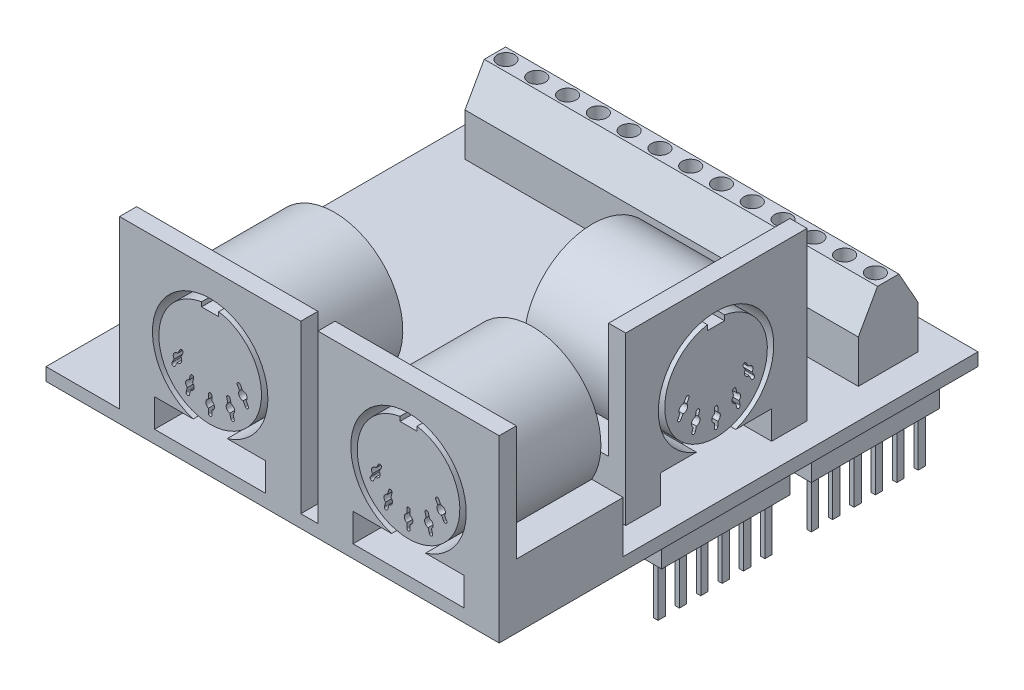
SolidWorks part; units mm, degrees
ref_plane "Front Plane" through (0, 0, 0) normal (0, 0, 1) x (1, 0, 0)
ref_plane "Top Plane" through (0, 0, 0) normal (0, 1, 0) x (1, 0, 0)
ref_plane "Right Plane" through (0, 0, 0) normal (1, 0, 0) x (0, 0, -1)
sketch "Sketch1" plane through (0, 0, 0) normal (0, 1, 0) x (1, 0, 0)
  line L1 (-26.5, -28) -> (26.5, -28)
  line L2 (-26.5, -28) -> (-26.5, 28)
  line L3 (-26.5, 28) -> (26.5, 28)
  line L4 (26.5, -28) -> (26.5, 28)
  line L5 (-26.5, -28) -> (26.5, 28) construction
  line L6 (-26.5, 28) -> (26.5, -28) construction
  point P0 (0, 0)
  dimension "D1" = 53
  dimension "D2" = 56
extrude "Boss-Extrude1" add sketch "Sketch1" along normal blind 1.5
sketch "Sketch2" plane through (0, 1.5, 0) normal (0, 1, 0) x (1, 0, 0)
  line L0 (-26.5, 28) -> (-26.5, -28) construction
  line L1 (-23, 24.5) -> (23, 24.5)
  line L2 (-23, 24.5) -> (-23, 17.5)
  line L3 (-23, 17.5) -> (23, 17.5)
  line L4 (23, 24.5) -> (23, 17.5)
  line L5 (26.5, -28) -> (26.5, 28) construction
  line L6 (26.5, 28) -> (-26.5, 28) construction
  dimension "D1" = 3.5
  dimension "D2" = 3.5
  dimension "D3" = 3.5
  dimension "D4" = 7
extrude "Boss-Extrude2" add sketch "Sketch2" along normal blind 5
sketch "Sketch4" plane through (-23, 0, 0) normal (-1, 0, 0) x (0, 0, 1)
  line L0 (-24.5, 6.5) -> (-17.5, 6.5)
  line L1 (-17.5, 6.5) -> (-19.75, 10.5)
  line L2 (-19.75, 10.5) -> (-22.25, 10.5)
  line L3 (-22.25, 10.5) -> (-24.5, 6.5)
  line L4 (-21, 10.5) -> (-21, 6.5) construction
  dimension "D1" = 4
  dimension "D2" = 2.5
extrude "Boss-Extrude3" add sketch "Sketch4" against normal up to surface (46 mm away) up to face at (23, 4, -21)
sketch "Sketch5" plane through (0, 10.5, 0) normal (0, 1, 0) x (1, 0, 0)
  line L0 (-23, 21) -> (23, 21) construction
  line L1 (-23, 24.5) -> (-23, 17.5) construction
  line L2 (23, 22.25) -> (23, 19.75) construction
  circle A0 centre (-21.7, 21) radius 1
  circle A1 centre (-18.1, 21) radius 1
  circle A2 centre (-14.5, 21) radius 1
  circle A3 centre (-10.9, 21) radius 1
  circle A4 centre (-7.3, 21) radius 1
  circle A5 centre (-3.7, 21) radius 1
  circle A6 centre (-0.1, 21) radius 1
  circle A7 centre (3.5, 21) radius 1
  circle A8 centre (7.1, 21) radius 1
  circle A9 centre (10.7, 21) radius 1
  circle A10 centre (14.3, 21) radius 1
  circle A11 centre (17.9, 21) radius 1
  circle A12 centre (21.5, 21) radius 1
  dimension "D1" = 2
  dimension "D2" = 1.3
  dimension "D3" = 13
extrude "Cut-Extrude1" cut sketch "Sketch5" against normal blind 2
sketch "Sketch6" plane through (0, 0, 28) normal (0, 0, 1) x (1, 0, 0)
  line L0 (-26.5, 1.5) -> (26.5, 1.5) construction
  line L1 (-17.9, 1.5) -> (3.3, 1.5)
  line L2 (-17.9, 1.5) -> (-17.9, 21)
  line L3 (-17.9, 21) -> (3.3, 21)
  line L4 (3.3, 1.5) -> (3.3, 21)
  line L5 (-23, 1.5) -> (23, 1.5) construction
  line L6 (5.3, 1.5) -> (26.5, 1.5)
  line L7 (5.3, 1.5) -> (5.3, 21)
  line L8 (5.3, 21) -> (26.5, 21)
  line L9 (26.5, 1.5) -> (26.5, 21)
  dimension "D1" = 21.2
  dimension "D2" = 19.5
  dimension "D3" = 21.2
  dimension "D4" = 19.5
  dimension "D5" = 2
extrude "Boss-Extrude4" add sketch "Sketch6" against normal blind 2 separate body
sketch "Sketch7" plane through (0, 0, 26) normal (0, 0, -1) x (-1, 0, 0)
  line L0 (-15.9, 21) -> (-15.9, 1.5) construction
  line L1 (-26.5, 21) -> (-5.3, 21) construction
  line L2 (-23, 1.5) -> (23, 1.5) construction
  line L3 (-15.9, 11.5) -> (7.2714, 11.5) construction
  line L4 (7.3, 21) -> (7.3, 7.5) construction
  line L5 (-3.3, 21) -> (17.9, 21) construction
  line L7 (-5.3, 21) -> (-5.3, 1.5) construction
  line L8 (-26.5, 1.5) -> (-5.3, 1.5)
  line L9 (-26.5, 1.5) -> (-26.5, 7.5)
  line L10 (-26.5, 7.5) -> (-22.8282, 7.5)
  line L12 (-5.3, 1.5) -> (-5.3, 7.5)
  line L13 (-8.9718, 7.5) -> (-5.3, 7.5)
  line L14 (-26.5, 1.5) -> (26.5, 1.5) construction
  line L15 (17.9, 7.5) -> (14.1996, 7.5)
  line L16 (17.9, 7.5) -> (17.9, 1.5)
  line L17 (17.9, 1.5) -> (-3.3, 1.5)
  line L18 (-3.3, 7.5) -> (-3.3, 1.5)
  line L19 (-3.3, 1.5) -> (-3.3, 21) construction
  line L20 (17.9, 21) -> (17.9, 1.5) construction
  line L21 (0.3432, 7.5) -> (-3.3, 7.5)
  line L22 (7.3, 3.5001) -> (7.3, 1.5) construction
  arc A0 (-8.9718, 7.5) -> (-22.8282, 7.5) centre (-15.9, 11.5) ccw
  arc A1 (14.1996, 7.5) -> (0.3432, 7.5) centre (7.2714, 11.5) ccw
  point P6 (-15.9, 11.5)
  dimension "D2" = 16
  dimension "D3" = 16
  dimension "D1" = 10
  dimension "D4" = 6
extrude "Boss-Extrude5" add sketch "Sketch7" along normal blind 12.5
sketch "Sketch8" plane through (0, 0, 28) normal (0, 0, 1) x (1, 0, 0)
  line L0 (-17.9, 21) -> (3.3, 1.5) construction
  line L1 (3.3, 21) -> (-17.9, 1.5) construction
  line L2 (-7.3, 17.25) -> (-7.3, 16.65) construction
  line L3 (-8.3, 16.65) -> (-6.3, 16.65)
  line L4 (-6.3, 16.65) -> (-6.3, 17.1661)
  line L5 (-8.3, 16.65) -> (-8.3, 17.1661)
  line L6 (-11.1219, 10.0698) -> (-3.4781, 10.0698) construction
  line L7 (-9.6748, 8.0313) -> (-4.9252, 8.0313) construction
  line L8 (-11.1219, 10.0698) -> (-9.6748, 8.0313) construction
  line L9 (-9.6748, 8.0313) -> (-7.3, 7.25) construction
  line L10 (-7.3, 7.25) -> (-4.9252, 8.0313) construction
  line L11 (-4.9252, 8.0313) -> (-3.4781, 10.0698) construction
  line L12 (-7.3, 6.25) -> (-7.3, 8.25) construction
  line L13 (-7.5, 6.25) -> (-7.5, 6.7917)
  line L14 (-7.1, 6.25) -> (-7.1, 6.7917)
  line L15 (-4.6757, 7.0629) -> (-5.1747, 8.9996) construction
  line L16 (-4.8694, 7.013) -> (-5.0046, 7.5376)
  line L17 (-4.4821, 7.1128) -> (-4.6172, 7.6374)
  line L18 (-3.0082, 9.1871) -> (-3.9479, 10.9526) construction
  line L19 (-3.1847, 9.0931) -> (-3.4393, 9.5713)
  line L20 (-2.8316, 9.2811) -> (-3.0862, 9.7593)
  line L21 (-9.9243, 7.0629) -> (-9.4253, 8.9996) construction
  line L22 (-10.1179, 7.1128) -> (-9.9828, 7.6374)
  line L23 (-9.7306, 7.013) -> (-9.5954, 7.5376)
  line L24 (-11.5918, 9.1871) -> (-10.6521, 10.9526) construction
  line L25 (-11.7684, 9.2811) -> (-11.5138, 9.7593)
  line L26 (-11.4153, 9.0931) -> (-11.1607, 9.5713)
  line L27 (-7.3, 17.25) -> (-10.6521, 10.9526) construction
  line L28 (-7.3, 17.25) -> (-3.9479, 10.9526) construction
  line L29 (-7.3, 17.25) -> (-9.4253, 8.9996) construction
  line L30 (-7.3, 17.25) -> (-5.1747, 8.9996) construction
  line L31 (-11.0832, 10.5683) -> (-10.8286, 11.0465)
  line L32 (-10.7301, 10.3804) -> (-10.4755, 10.8586)
  line L33 (4.3, 1.5) -> (4.3, 27.7192) construction
  line L34 (-9.7542, 8.5249) -> (-9.619, 9.0495)
  line L35 (-9.3668, 8.4251) -> (-9.2317, 8.9497)
  line L36 (3.3, 1.5) -> (5.3, 1.5) construction
  line L37 (15.9, 1.5) -> (15.9, 11.25) construction
  line L38 (-7.5, 7.7083) -> (-7.5, 8.25)
  line L39 (-7.1, 7.7083) -> (-7.1, 8.25)
  line L40 (15.9, 17.25) -> (13.7747, 8.9996) construction
  line L41 (15.9, 17.25) -> (18.0253, 8.9996) construction
  line L42 (-5.2332, 8.4251) -> (-5.3683, 8.9497)
  line L43 (-4.8458, 8.5249) -> (-4.981, 9.0495)
  line L44 (15.9, 17.25) -> (12.5479, 10.9526) construction
  line L45 (15.9, 17.25) -> (19.2521, 10.9526) construction
  line L46 (-3.8699, 10.3804) -> (-4.1245, 10.8586)
  line L47 (-3.5168, 10.5683) -> (-3.7714, 11.0465)
  line L48 (20.1918, 9.1871) -> (19.2521, 10.9526) construction
  line L49 (18.5243, 7.0629) -> (18.0253, 8.9996) construction
  line L50 (11.6082, 9.1871) -> (12.5479, 10.9526) construction
  line L51 (13.2757, 7.0629) -> (13.7747, 8.9996) construction
  line L52 (15.9, 6.25) -> (15.9, 8.25) construction
  line L53 (13.5252, 8.0313) -> (12.0781, 10.0698) construction
  line L54 (15.9, 7.25) -> (13.5252, 8.0313) construction
  line L55 (18.2748, 8.0313) -> (15.9, 7.25) construction
  line L56 (19.7219, 10.0698) -> (18.2748, 8.0313) construction
  line L57 (18.2748, 8.0313) -> (13.5252, 8.0313) construction
  line L58 (19.7219, 10.0698) -> (12.0781, 10.0698) construction
  line L59 (15.9, 17.25) -> (15.9, 16.65) construction
  line L60 (17.89, 4.8) -> (22.4, 4.8)
  line L61 (22.4, 4.8) -> (22.4, 1.5)
  line L62 (9.4, 4.8) -> (13.91, 4.8)
  line L63 (9.4, 1.5) -> (9.4, 4.8)
  line L64 (22.4, 1.5) -> (9.4, 1.5)
  line L65 (12.1168, 10.5683) -> (12.3714, 11.0465)
  line L66 (12.4699, 10.3804) -> (12.7245, 10.8586)
  line L67 (13.4458, 8.5249) -> (13.581, 9.0495)
  line L68 (13.8332, 8.4251) -> (13.9683, 8.9497)
  line L69 (15.7, 7.7083) -> (15.7, 8.25)
  line L70 (16.1, 7.7083) -> (16.1, 8.25)
  line L71 (17.9668, 8.4251) -> (17.8317, 8.9497)
  line L72 (18.3542, 8.5249) -> (18.219, 9.0495)
  line L73 (19.3301, 10.3804) -> (19.0755, 10.8586)
  line L74 (19.6832, 10.5683) -> (19.4286, 11.0465)
  line L75 (20.0153, 9.0931) -> (19.7607, 9.5713)
  line L76 (20.3684, 9.2811) -> (20.1138, 9.7593)
  line L77 (18.3306, 7.013) -> (18.1954, 7.5376)
  line L78 (18.7179, 7.1128) -> (18.5828, 7.6374)
  line L79 (11.4316, 9.2811) -> (11.6862, 9.7593)
  line L80 (11.7847, 9.0931) -> (12.0393, 9.5713)
  line L81 (13.0821, 7.1128) -> (13.2172, 7.6374)
  line L82 (-17.9, 1.5) -> (3.3, 1.5) construction
  line L83 (-13.8, 1.5) -> (-0.8, 1.5)
  line L84 (-0.8, 1.5) -> (-0.8, 4.8)
  line L85 (-0.8, 4.8) -> (-5.31, 4.8)
  line L86 (-13.8, 4.8) -> (-13.8, 1.5)
  line L87 (-7.3, 1.5) -> (-7.3, 11.25) construction
  line L88 (-9.29, 4.8) -> (-13.8, 4.8)
  line L89 (13.4694, 7.013) -> (13.6046, 7.5376)
  line L90 (15.7, 6.25) -> (15.7, 6.7917)
  line L91 (16.1, 6.25) -> (16.1, 6.7917)
  line L92 (16.9, 16.65) -> (16.9, 17.1661)
  line L93 (14.9, 16.65) -> (14.9, 17.1661)
  line L94 (16.9, 16.65) -> (14.9, 16.65)
  arc A0 (-5.31, 4.8) -> (-9.29, 4.8) centre (-7.3, 11.25) ccw
  arc A1 (-8.3, 17.1661) -> (-6.3, 17.1661) centre (-7.3, 11.25) ccw
  arc A2 (-7.5, 7.7083) -> (-7.5, 6.7917) centre (-7.3, 7.25) ccw
  arc A3 (-9.5954, 7.5376) -> (-9.3668, 8.4251) centre (-9.6748, 8.0313) ccw
  arc A4 (-4.8005, 7.5471) -> (-4.8458, 8.5249) centre (-4.9252, 8.0313) ccw
  arc A5 (-3.0862, 9.7593) -> (-3.5168, 10.5683) centre (-3.4781, 10.0698) ccw
  arc A6 (-11.0832, 10.5683) -> (-11.5138, 9.7593) centre (-11.1219, 10.0698) ccw
  circle A7 centre (-7.3, 11.25) radius 4 construction
  arc A8 (-7.5, 6.25) -> (-7.1, 6.25) centre (-7.3, 6.25) ccw
  arc A9 (-7.1, 8.25) -> (-7.5, 8.25) centre (-7.3, 8.25) ccw
  arc A10 (-4.8694, 7.013) -> (-4.4821, 7.1128) centre (-4.6757, 7.0629) ccw
  arc A11 (-4.981, 9.0495) -> (-5.3683, 8.9497) centre (-5.1747, 8.9996) ccw
  arc A12 (-3.1847, 9.0931) -> (-2.8316, 9.2811) centre (-3.0082, 9.1871) ccw
  arc A13 (-3.7714, 11.0465) -> (-4.1245, 10.8586) centre (-3.9479, 10.9526) ccw
  arc A14 (-10.1179, 7.1128) -> (-9.7306, 7.013) centre (-9.9243, 7.0629) ccw
  arc A15 (-9.2317, 8.9497) -> (-9.619, 9.0495) centre (-9.4253, 8.9996) ccw
  arc A16 (-11.7684, 9.2811) -> (-11.4153, 9.0931) centre (-11.5918, 9.1871) ccw
  arc A17 (-10.4755, 10.8586) -> (-10.8286, 11.0465) centre (-10.6521, 10.9526) ccw
  arc A18 (-11.1607, 9.5713) -> (-10.7301, 10.3804) centre (-11.1219, 10.0698) ccw
  arc A19 (-9.7542, 8.5249) -> (-9.9828, 7.6374) centre (-9.6748, 8.0313) ccw
  arc A20 (-7.1, 6.7917) -> (-7.1, 7.7083) centre (-7.3, 7.25) ccw
  arc A21 (-5.2332, 8.4251) -> (-5.0046, 7.5376) centre (-4.9252, 8.0313) ccw
  arc A22 (-3.8699, 10.3804) -> (-3.4393, 9.5713) centre (-3.4781, 10.0698) ccw
  circle A23 centre (15.9, 11.25) radius 4 construction
  arc A24 (12.4699, 10.3804) -> (12.0393, 9.5713) centre (12.0781, 10.0698) cw
  arc A25 (13.8332, 8.4251) -> (13.6046, 7.5376) centre (13.5252, 8.0313) cw
  arc A26 (15.7, 6.7917) -> (15.7, 7.7083) centre (15.9, 7.25) cw
  arc A27 (18.3542, 8.5249) -> (18.5828, 7.6374) centre (18.2748, 8.0313) cw
  arc A28 (19.7607, 9.5713) -> (19.3301, 10.3804) centre (19.7219, 10.0698) cw
  arc A29 (19.0755, 10.8586) -> (19.4286, 11.0465) centre (19.2521, 10.9526) cw
  arc A30 (20.3684, 9.2811) -> (20.0153, 9.0931) centre (20.1918, 9.1871) cw
  arc A31 (17.8317, 8.9497) -> (18.219, 9.0495) centre (18.0253, 8.9996) cw
  arc A32 (18.7179, 7.1128) -> (18.3306, 7.013) centre (18.5243, 7.0629) cw
  arc A33 (12.3714, 11.0465) -> (12.7245, 10.8586) centre (12.5479, 10.9526) cw
  arc A34 (11.7847, 9.0931) -> (11.4316, 9.2811) centre (11.6082, 9.1871) cw
  arc A35 (13.581, 9.0495) -> (13.9683, 8.9497) centre (13.7747, 8.9996) cw
  arc A36 (13.4694, 7.013) -> (13.0821, 7.1128) centre (13.2757, 7.0629) cw
  arc A37 (15.7, 8.25) -> (16.1, 8.25) centre (15.9, 8.25) cw
  arc A38 (16.1, 6.25) -> (15.7, 6.25) centre (15.9, 6.25) cw
  arc A39 (19.6832, 10.5683) -> (20.1138, 9.7593) centre (19.7219, 10.0698) cw
  arc A40 (11.6862, 9.7593) -> (12.1168, 10.5683) centre (12.0781, 10.0698) cw
  arc A41 (13.4005, 7.5471) -> (13.4458, 8.5249) centre (13.5252, 8.0313) cw
  arc A42 (18.1954, 7.5376) -> (17.9668, 8.4251) centre (18.2748, 8.0313) cw
  arc A43 (16.1, 7.7083) -> (16.1, 6.7917) centre (15.9, 7.25) cw
  arc A44 (16.9, 17.1661) -> (14.9, 17.1661) centre (15.9, 11.25) cw
  arc A45 (13.91, 4.8) -> (17.89, 4.8) centre (15.9, 11.25) cw
  point P8 (-7.3, 11.25)
  point P30 (-7.3, 7.25)
  point P37 (-4.9252, 8.0313)
  point P44 (-3.4781, 10.0698)
  point P50 (-9.6748, 8.0313)
  point P58 (-11.1219, 10.0698)
  dimension "D1" = 13.5
  dimension "D2" = 12
  dimension "D4" = 1
  dimension "D5" = 8
  dimension "D8" = 0.2
  dimension "D3" = 2
  dimension "D6" = 2.5
  dimension "D7" = 2
  dimension "D9" = 3.3
  dimension "D10" = 13
  dimension "D11" = 0.6
extrude "Cut-Extrude2" cut sketch "Sketch8" against normal blind 5 contours A0 A1 L5 L3 L4 | L26 A18 L32 A17 L31 A6 L25 A16 | L34 A19 L22 A14 L23 A3 L35 A15 | L14 A20 L39 A9 L38 A2 L13 A8 | L42 A21 L16 A10 L17 A4 L43 A11 | L46 A22 L19 A12 L20 A5 L47 A13 | A44 L61 | A40 L79 A34 L80 A24 L66 A33 L65 | A36 L89 A25 L68 A35 L67 | A43 L70 A37 L69 A26 L90 A38 L91 | A42 L77 A32 L78 A27 L72 A31 L71 | A39 L74 A29 L73 A28 L75 A30 L76 region at (-7.3, 7.25, 28) region at (-4.9252, 8.0313, 28) region at (-3.4781, 10.0698, 28) region at (-9.6748, 8.0312, 28) region at (-11.1219, 10.0698, 28) region at (20.145, 4.5868, 28) region at (12.0781, 10.0698, 28) region at (13.5252, 8.0313, 28) region at (15.9, 7.25, 28) region at (18.2748, 8.0312, 28) region at (19.7219, 10.0698, 28) region at (-13.5868, 3.15, 28)
sketch "Sketch9" plane through (26.5, 0, 0) normal (1, 0, 0) x (0, 0, -1)
  line L0 (-13.5, 1.5) -> (28, 1.5) construction
  line L1 (-10.2, 1.5) -> (11, 1.5)
  line L2 (-10.2, 1.5) -> (-10.2, 21)
  line L3 (-10.2, 21) -> (11, 21)
  line L4 (11, 1.5) -> (11, 21)
  line L5 (-26, 21) -> (-28, 21) construction
  line L7 (-28, 21) -> (-28, 0) construction
  dimension "D1" = 21.2
  dimension "D2" = 39
extrude "Boss-Extrude6" add sketch "Sketch9" against normal blind 2 from offset 3 separate body offset against normal yes
sketch "Sketch11" plane through (21.5, 0, 0) normal (-1, 0, 0) x (0, 0, 1)
  line L0 (-0.4, 21) -> (-0.4, 1.5) construction
  line L1 (-11, 21) -> (10.2, 21) construction
  line L2 (10.2, 1.5) -> (-11, 1.5) construction
  line L3 (10.2, 21) -> (10.2, 1.5) construction
  line L4 (-11, 1.5) -> (10.2, 1.5)
  line L5 (-11, 1.5) -> (-11, 7.5)
  line L6 (-11, 7.5) -> (-7.3282, 7.5)
  line L7 (10.2, 1.5) -> (10.2, 7.5)
  line L8 (6.5282, 7.5) -> (10.2, 7.5)
  arc A0 (6.5282, 7.5) -> (-7.3282, 7.5) centre (-0.4, 11.5) ccw
  dimension "D2" = 16
  dimension "D1" = 10
  dimension "D3" = 6
extrude "Boss-Extrude7" add sketch "Sketch11" along normal blind 12.5
sketch "Sketch13" plane through (23.5, 0, 0) normal (1, 0, 0) x (0, 0, -1)
  line L0 (-10.2, 21) -> (11, 1.5) construction
  line L1 (-10.2, 1.5) -> (11, 1.5) construction
  line L2 (0.3632, 16.1486) -> (0.3632, 1.5) construction
  line L3 (-6.1, 1.5) -> (6.8265, 1.5)
  line L7 (0.3632, 17.0631) -> (0.3632, 16.4631) construction
  line L8 (-0.6368, 16.4631) -> (1.3632, 16.4631)
  line L9 (1.3632, 16.4631) -> (1.3632, 17.0631)
  line L10 (-0.6368, 16.4631) -> (-0.6368, 17.0631)
  line L11 (-3.4587, 9.9668) -> (4.1852, 9.9668) construction
  line L12 (-2.0116, 7.9283) -> (2.738, 7.9283) construction
  line L13 (-3.4587, 9.9668) -> (-2.0116, 7.9283) construction
  line L14 (-2.0116, 7.9283) -> (0.3632, 7.147) construction
  line L15 (0.3632, 7.147) -> (2.738, 7.9283) construction
  line L16 (2.738, 7.9283) -> (4.1852, 9.9668) construction
  line L17 (0.3632, 6.147) -> (0.3632, 8.147) construction
  line L18 (0.1633, 6.1525) -> (0.1633, 6.6887)
  line L19 (0.5631, 6.1534) -> (0.5631, 6.6887)
  line L20 (2.9896, 6.9604) -> (2.4864, 8.8961) construction
  line L21 (2.7897, 6.9582) -> (2.6661, 7.4335)
  line L22 (3.186, 6.9982) -> (3.0465, 7.5348)
  line L23 (4.6594, 9.0864) -> (3.711, 10.8473) construction
  line L24 (4.4753, 9.0081) -> (4.2273, 9.4686)
  line L25 (4.8354, 9.1812) -> (4.5786, 9.6582)
  line L26 (-2.2632, 6.9604) -> (-1.7599, 8.8961) construction
  line L27 (-2.4567, 7.0108) -> (-2.3204, 7.535)
  line L28 (-2.0696, 6.9101) -> (-1.9333, 7.4344)
  line L29 (-3.9329, 9.0864) -> (-2.9845, 10.8473) construction
  line L30 (-4.1058, 9.1869) -> (-3.852, 9.6581)
  line L31 (-3.7568, 8.9916) -> (-3.4999, 9.4685)
  line L32 (0.3632, 17.0631) -> (-2.9845, 10.8473) construction
  line L33 (0.3632, 17.0631) -> (3.711, 10.8473) construction
  line L34 (0.3632, 17.0631) -> (-1.7599, 8.8961) construction
  line L35 (0.3632, 17.0631) -> (2.4864, 8.8961) construction
  line L36 (-3.4174, 10.4651) -> (-3.1636, 10.9363)
  line L37 (-3.0653, 10.2755) -> (-2.8084, 10.7524)
  line L38 (-2.0897, 8.4221) -> (-1.9519, 8.9523)
  line L39 (-1.7027, 8.3215) -> (-1.5664, 8.8458)
  line L40 (0.1633, 7.6053) -> (0.1633, 8.153)
  line L41 (0.5631, 7.6053) -> (0.5631, 8.1534)
  line L42 (2.4366, 8.3272) -> (2.2866, 8.9043)
  line L43 (2.8159, 8.4222) -> (2.6828, 8.9339)
  line L44 (3.7918, 10.2755) -> (3.5349, 10.7524)
  line L45 (4.144, 10.4651) -> (3.8871, 10.9421)
  line L46 (-6.1368, 1.5) -> (6.8632, 1.5)
  line L47 (6.8632, 1.5) -> (6.8632, 4.8)
  line L48 (6.8632, 4.8) -> (2.6606, 4.8)
  line L49 (-6.1368, 4.8) -> (-6.1368, 1.5)
  line L50 (0.3632, 1.5) -> (0.3632, 11.147) construction
  line L51 (-1.9342, 4.8) -> (-6.1368, 4.8)
  arc A2 (2.6606, 4.8) -> (-1.9342, 4.8) centre (0.3632, 11.147) ccw
  arc A3 (-0.6368, 17.0631) -> (1.3632, 17.0631) centre (0.3632, 11.147) ccw
  arc A4 (0.1633, 7.6053) -> (0.1633, 6.6887) centre (0.3632, 7.147) ccw
  arc A5 (-1.9333, 7.4344) -> (-1.7027, 8.3215) centre (-2.0116, 7.9283) ccw
  arc A6 (3.0465, 7.5348) -> (2.8159, 8.4222) centre (2.738, 7.9283) ccw
  arc A7 (4.5786, 9.6582) -> (4.144, 10.4651) centre (4.1852, 9.9668) ccw
  arc A8 (-3.4174, 10.4651) -> (-3.852, 9.6581) centre (-3.4587, 9.9668) ccw
  circle A9 centre (0.3632, 11.147) radius 4 construction
  arc A10 (0.1633, 6.1525) -> (0.5631, 6.1534) centre (0.3632, 6.147) ccw
  arc A11 (0.5631, 8.1534) -> (0.1633, 8.153) centre (0.3632, 8.147) ccw
  arc A12 (2.7897, 6.9582) -> (3.186, 6.9982) centre (2.9896, 6.9604) ccw
  arc A13 (2.6828, 8.9339) -> (2.2866, 8.9043) centre (2.4864, 8.8961) ccw
  arc A14 (4.4753, 9.0081) -> (4.8354, 9.1812) centre (4.6594, 9.0864) ccw
  arc A15 (3.8871, 10.9421) -> (3.5349, 10.7524) centre (3.711, 10.8473) ccw
  arc A16 (-2.4567, 7.0108) -> (-2.0696, 6.9101) centre (-2.2632, 6.9604) ccw
  arc A17 (-1.5664, 8.8458) -> (-1.9519, 8.9523) centre (-1.7599, 8.8961) ccw
  arc A18 (-4.1058, 9.1869) -> (-3.7568, 8.9916) centre (-3.9329, 9.0864) ccw
  arc A19 (-2.8084, 10.7524) -> (-3.1636, 10.9363) centre (-2.9845, 10.8473) ccw
  arc A20 (-3.4999, 9.4685) -> (-3.0653, 10.2755) centre (-3.4587, 9.9668) ccw
  arc A21 (-2.0897, 8.4221) -> (-2.3204, 7.535) centre (-2.0116, 7.9283) ccw
  arc A22 (0.5631, 6.6887) -> (0.5631, 7.6053) centre (0.3632, 7.147) ccw
  arc A23 (2.4366, 8.3272) -> (2.6661, 7.4335) centre (2.738, 7.9283) ccw
  arc A24 (3.7918, 10.2755) -> (4.2273, 9.4686) centre (4.1852, 9.9668) ccw
  point P15 (0.3632, 11.147)
  point P35 (0.3632, 7.147)
  point P42 (2.738, 7.9283)
  point P49 (4.1852, 9.9668)
  point P55 (-2.0116, 7.9283)
  point P63 (-3.4587, 9.9668)
  point P93 (0.4, 11.25)
  line M4 (-10.2, 1.5) -> (11, 1.5)
  dimension "D2" = 13
  dimension "D6" = 1
  dimension "D7" = 8
  dimension "D10" = 0.2
  dimension "D3" = 6.75
  dimension "D12" = 6
  dimension "D13" = 0.2
  dimension "D4" = 3.3
  dimension "D5" = 2
  dimension "D8" = 2.5
  dimension "D9" = 2
  dimension "D11" = 0.6
extrude "Cut-Extrude3" cut sketch "Sketch13" against normal blind 5 contours L48 A2 L51 L49 L47 A3 L10 L8 L9 M4 | L38 A21 L27 A16 L28 A5 L39 A17 | L31 A20 L37 A19 L36 A8 L30 A18 | L19 A22 L41 A11 L40 A4 L18 A10 | L42 A23 L21 A12 L22 A6 L43 A13 | L44 A24 L24 A14 L25 A7 L45 A15 region at (23.5, 1.7124, 6.1184) region at (23.5, 7.147, -0.3632) region at (23.5, 7.9274, -2.7394) region at (23.5, 9.9671, -4.1851) region at (23.5, 7.9282, 2.0116) region at (23.5, 9.9668, 3.4587)
sketch "Sketch14" plane through (0, 0, 0) normal (0, -1, 0) x (1, 0, 0)
  line L0 (25.5, 28) -> (25.5, -28) construction
  line L3 (-26.5, 28) -> (26.5, 28) construction
  line L4 (26.5, -28) -> (-26.5, -28) construction
  line L5 (-25.5, 28) -> (-25.5, -28) construction
  line L6 (26.5, 28) -> (26.5, -28) construction
  line L7 (-26.5, -28) -> (-26.5, 28) construction
  line L9 (-25.5, 18) -> (-23, 18)
  line L10 (-25.5, 18) -> (-25.5, -2)
  line L11 (-25.5, -2) -> (-23, -2)
  line L12 (-23, 18) -> (-23, -2)
  line L13 (25.5, 8) -> (23, 8)
  line L14 (25.5, 8) -> (25.5, -7)
  line L15 (25.5, -7) -> (23, -7)
  line L16 (23, 8) -> (23, -7)
  line L17 (25.5, -9.5) -> (23, -9.5)
  line L18 (25.5, -9.5) -> (25.5, -24.5)
  line L19 (25.5, -24.5) -> (23, -24.5)
  line L20 (23, -9.5) -> (23, -24.5)
  line L21 (-25.5, -4.5) -> (-23, -4.5)
  line L22 (-25.5, -4.5) -> (-25.5, -24.5)
  line L23 (-25.5, -24.5) -> (-23, -24.5)
  line L24 (-23, -4.5) -> (-23, -24.5)
  dimension "D1" = 1
  dimension "D2" = 1
  dimension "D3" = 2.5
  dimension "D4" = 20
  dimension "D5" = 15
  dimension "D6" = 3.5
  dimension "D7" = 15
  dimension "D8" = 2.5
  dimension "D9" = 10
  dimension "D10" = 2.5
  dimension "D11" = 20
  dimension "D12" = 2.5
  dimension "D13" = 20
  dimension "D14" = 3.5
extrude "Boss-Extrude8" add sketch "Sketch14" along normal blind 3
sketch "Sketch15" plane through (0, -3, 0) normal (0, -1, 0) x (1, 0, 0)
  line L0 (24.25, 8) -> (24.25, -24.5) construction
  line L1 (25.5, 8) -> (23, 8) construction
  line L2 (23, -24.5) -> (25.5, -24.5) construction
  line L3 (24, 4.925) -> (24.5, 4.925)
  line L4 (24, 7.425) -> (24.5, 7.425)
  line L5 (24, 7.425) -> (24, 6.575)
  line L6 (24, 6.575) -> (24.5, 6.575)
  line L7 (24.5, 7.425) -> (24.5, 6.575)
  line L8 (24, 7.425) -> (24.5, 6.575) construction
  line L9 (24, 6.575) -> (24.5, 7.425) construction
  line L10 (24, 4.925) -> (24, 4.075)
  line L11 (24, 4.075) -> (24.5, 4.075)
  line L12 (24.5, 4.925) -> (24.5, 4.075)
  line L13 (24, 4.925) -> (24.5, 4.075) construction
  line L14 (24, 4.075) -> (24.5, 4.925) construction
  line L15 (24, 2.425) -> (24.5, 2.425)
  line L16 (24, 2.425) -> (24, 1.575)
  line L17 (24, 1.575) -> (24.5, 1.575)
  line L18 (24.5, 2.425) -> (24.5, 1.575)
  line L19 (24, 2.425) -> (24.5, 1.575) construction
  line L20 (24, 1.575) -> (24.5, 2.425) construction
  line L21 (24, -0.075) -> (24.5, -0.075)
  line L22 (24, -0.075) -> (24, -0.925)
  line L23 (24, -0.925) -> (24.5, -0.925)
  line L24 (24.5, -0.075) -> (24.5, -0.925)
  line L25 (24, -0.075) -> (24.5, -0.925) construction
  line L26 (24, -0.925) -> (24.5, -0.075) construction
  line L27 (24, -2.575) -> (24.5, -2.575)
  line L28 (24, -2.575) -> (24, -3.425)
  line L29 (24, -3.425) -> (24.5, -3.425)
  line L30 (24.5, -2.575) -> (24.5, -3.425)
  line L31 (24, -2.575) -> (24.5, -3.425) construction
  line L32 (24, -3.425) -> (24.5, -2.575) construction
  line L33 (24, -5.075) -> (24.5, -5.075)
  line L34 (24, -5.075) -> (24, -5.925)
  line L35 (24, -5.925) -> (24.5, -5.925)
  line L36 (24.5, -5.075) -> (24.5, -5.925)
  line L37 (24, -5.075) -> (24.5, -5.925) construction
  line L38 (24, -5.925) -> (24.5, -5.075) construction
  line L42 (25.5, -9.5) -> (23, -9.5) construction
  line L43 (24, -10.5) -> (24.5, -10.5)
  line L44 (24, -10.5) -> (24, -11.35)
  line L45 (24, -11.35) -> (24.5, -11.35)
  line L46 (24.5, -10.5) -> (24.5, -11.35)
  line L47 (24, -10.5) -> (24.5, -11.35) construction
  line L48 (24, -11.35) -> (24.5, -10.5) construction
  line L49 (24, -13) -> (24, -13.85)
  line L50 (24, -13.85) -> (24.5, -13.85)
  line L51 (24.5, -13) -> (24.5, -13.85)
  line L52 (24, -13) -> (24.5, -13)
  line L53 (24, -15.5) -> (24, -16.35)
  line L54 (24, -16.35) -> (24.5, -16.35)
  line L55 (24.5, -15.5) -> (24.5, -16.35)
  line L56 (24, -15.5) -> (24.5, -15.5)
  line L57 (24, -18) -> (24, -18.85)
  line L58 (24, -18.85) -> (24.5, -18.85)
  line L59 (24.5, -18) -> (24.5, -18.85)
  line L60 (24, -18) -> (24.5, -18)
  line L61 (24, -20.5) -> (24, -21.35)
  line L62 (24, -21.35) -> (24.5, -21.35)
  line L63 (24.5, -20.5) -> (24.5, -21.35)
  line L64 (24, -20.5) -> (24.5, -20.5)
  line L65 (24, -23) -> (24, -23.85)
  line L66 (24, -23.85) -> (24.5, -23.85)
  line L67 (24.5, -23) -> (24.5, -23.85)
  line L68 (24, -23) -> (24.5, -23)
  line L70 (-24.25, 18) -> (-24.25, -24.5) construction
  line L71 (-23, 18) -> (-25.5, 18) construction
  line L72 (-25.5, -24.5) -> (-23, -24.5) construction
  line L73 (-24.5, 14.5) -> (-24, 14.5)
  line L74 (-24.5, 17) -> (-24, 17)
  line L75 (-24.5, 17) -> (-24.5, 16.15)
  line L76 (-24.5, 16.15) -> (-24, 16.15)
  line L77 (-24, 17) -> (-24, 16.15)
  line L78 (-24.5, 17) -> (-24, 16.15) construction
  line L79 (-24.5, 16.15) -> (-24, 17) construction
  line L80 (-24.5, 14.5) -> (-24.5, 13.65)
  line L81 (-24.5, 13.65) -> (-24, 13.65)
  line L82 (-24, 14.5) -> (-24, 13.65)
  line L83 (-24.5, 14.5) -> (-24, 13.65) construction
  line L84 (-24.5, 13.65) -> (-24, 14.5) construction
  line L85 (-24.5, 12) -> (-24, 12)
  line L86 (-24.5, 12) -> (-24.5, 11.15)
  line L87 (-24.5, 11.15) -> (-24, 11.15)
  line L88 (-24, 12) -> (-24, 11.15)
  line L89 (-24.5, 12) -> (-24, 11.15) construction
  line L90 (-24.5, 11.15) -> (-24, 12) construction
  line L91 (-24.5, 9.5) -> (-24, 9.5)
  line L92 (-24.5, 9.5) -> (-24.5, 8.65)
  line L93 (-24.5, 8.65) -> (-24, 8.65)
  line L94 (-24, 9.5) -> (-24, 8.65)
  line L95 (-24.5, 9.5) -> (-24, 8.65) construction
  line L96 (-24.5, 8.65) -> (-24, 9.5) construction
  line L97 (-24.5, 7) -> (-24, 7)
  line L98 (-24.5, 7) -> (-24.5, 6.15)
  line L99 (-24.5, 6.15) -> (-24, 6.15)
  line L100 (-24, 7) -> (-24, 6.15)
  line L101 (-24.5, 7) -> (-24, 6.15) construction
  line L102 (-24.5, 6.15) -> (-24, 7) construction
  line L103 (-24.5, 4.5) -> (-24, 4.5)
  line L104 (-24.5, 4.5) -> (-24.5, 3.65)
  line L105 (-24.5, 3.65) -> (-24, 3.65)
  line L106 (-24, 4.5) -> (-24, 3.65)
  line L107 (-24.5, 4.5) -> (-24, 3.65) construction
  line L108 (-24.5, 3.65) -> (-24, 4.5) construction
  line L109 (-24.5, 2) -> (-24, 2)
  line L110 (-24.5, 2) -> (-24.5, 1.15)
  line L111 (-24.5, 1.15) -> (-24, 1.15)
  line L112 (-24, 2) -> (-24, 1.15)
  line L113 (-24.5, 2) -> (-24, 1.15) construction
  line L114 (-24.5, 1.15) -> (-24, 2) construction
  line L115 (-24.5, -0.5) -> (-24, -0.5)
  line L116 (-24.5, -0.5) -> (-24.5, -1.35)
  line L117 (-24.5, -1.35) -> (-24, -1.35)
  line L118 (-24, -0.5) -> (-24, -1.35)
  line L119 (-24.5, -0.5) -> (-24, -1.35) construction
  line L120 (-24.5, -1.35) -> (-24, -0.5) construction
  line L121 (-24.25, -3.25) -> (-28.1143, -3.25) construction
  line L122 (-24.5, -5.15) -> (-24, -6) construction
  line L123 (-24.5, -6) -> (-24, -5.15) construction
  line L124 (-24.5, -7.65) -> (-24, -8.5) construction
  line L125 (-24.5, -8.5) -> (-24, -7.65) construction
  line L126 (-24.5, -10.15) -> (-24, -11) construction
  line L127 (-24.5, -11) -> (-24, -10.15) construction
  line L128 (-24.5, -12.65) -> (-24, -13.5) construction
  line L129 (-24.5, -13.5) -> (-24, -12.65) construction
  line L130 (-24.5, -15.15) -> (-24, -16) construction
  line L131 (-24.5, -16) -> (-24, -15.15) construction
  line L132 (-24.5, -17.65) -> (-24, -18.5) construction
  line L133 (-24.5, -18.5) -> (-24, -17.65) construction
  line L134 (-24.5, -20.15) -> (-24, -21) construction
  line L135 (-24.5, -21) -> (-24, -20.15) construction
  line L136 (-24.5, -22.65) -> (-24, -23.5) construction
  line L137 (-24.5, -23.5) -> (-24, -22.65) construction
  line L138 (-24, -6) -> (-24, -5.15)
  line L139 (-24.5, -5.15) -> (-24, -5.15)
  line L140 (-24.5, -6) -> (-24.5, -5.15)
  line L141 (-24.5, -6) -> (-24, -6)
  line L142 (-24, -8.5) -> (-24, -7.65)
  line L143 (-24.5, -7.65) -> (-24, -7.65)
  line L144 (-24.5, -8.5) -> (-24.5, -7.65)
  line L145 (-24.5, -8.5) -> (-24, -8.5)
  line L146 (-24, -11) -> (-24, -10.15)
  line L147 (-24.5, -10.15) -> (-24, -10.15)
  line L148 (-24.5, -11) -> (-24.5, -10.15)
  line L149 (-24.5, -11) -> (-24, -11)
  line L150 (-24, -13.5) -> (-24, -12.65)
  line L151 (-24.5, -12.65) -> (-24, -12.65)
  line L152 (-24.5, -13.5) -> (-24.5, -12.65)
  line L153 (-24.5, -13.5) -> (-24, -13.5)
  line L154 (-24, -16) -> (-24, -15.15)
  line L155 (-24.5, -15.15) -> (-24, -15.15)
  line L156 (-24.5, -16) -> (-24.5, -15.15)
  line L157 (-24.5, -16) -> (-24, -16)
  line L158 (-24, -18.5) -> (-24, -17.65)
  line L159 (-24.5, -17.65) -> (-24, -17.65)
  line L160 (-24.5, -18.5) -> (-24.5, -17.65)
  line L161 (-24.5, -18.5) -> (-24, -18.5)
  line L162 (-24, -21) -> (-24, -20.15)
  line L163 (-24.5, -20.15) -> (-24, -20.15)
  line L164 (-24.5, -21) -> (-24.5, -20.15)
  line L165 (-24, -23.5) -> (-24, -22.65)
  line L166 (-24.5, -22.65) -> (-24, -22.65)
  line L167 (-24.5, -23.5) -> (-24.5, -22.65)
  line L168 (-24.5, -23.5) -> (-24, -23.5)
  line L169 (-24.5, -21) -> (-24, -21)
  point P6 (24.25, 7)
  point P13 (24.25, 4.5)
  point P18 (24.25, 2)
  point P23 (24.25, -0.5)
  point P28 (24.25, -3)
  point P33 (24.25, -5.5)
  point P38 (24.25, -10.925)
  point P43 (-24.25, 16.575)
  point P76 (-24.25, 14.075)
  point P81 (-24.25, 11.575)
  point P86 (-24.25, 9.075)
  point P91 (-24.25, 6.575)
  point P96 (-24.25, 4.075)
  point P101 (-24.25, 1.575)
  point P106 (-24.25, -0.925)
  point P143 (-24.25, -5.575)
  point P144 (-24.25, -8.075)
  point P145 (-24.25, -10.575)
  point P146 (-24.25, -13.075)
  point P147 (-24.25, -15.575)
  point P148 (-24.25, -18.075)
  point P149 (-24.25, -20.575)
  point P150 (-24.25, -23.075)
  dimension "D1" = 0.5
  dimension "D2" = 0.85
  dimension "D3" = 1
  dimension "D5" = 0.5
  dimension "D6" = 0.85
  dimension "D7" = 1
  dimension "D9" = 1
  dimension "D10" = 0.5
  dimension "D11" = 0.85
  dimension "D4" = 6
  dimension "D8" = 6
  dimension "D12" = 8
extrude "Boss-Extrude9" add sketch "Sketch15" along normal blind 6
